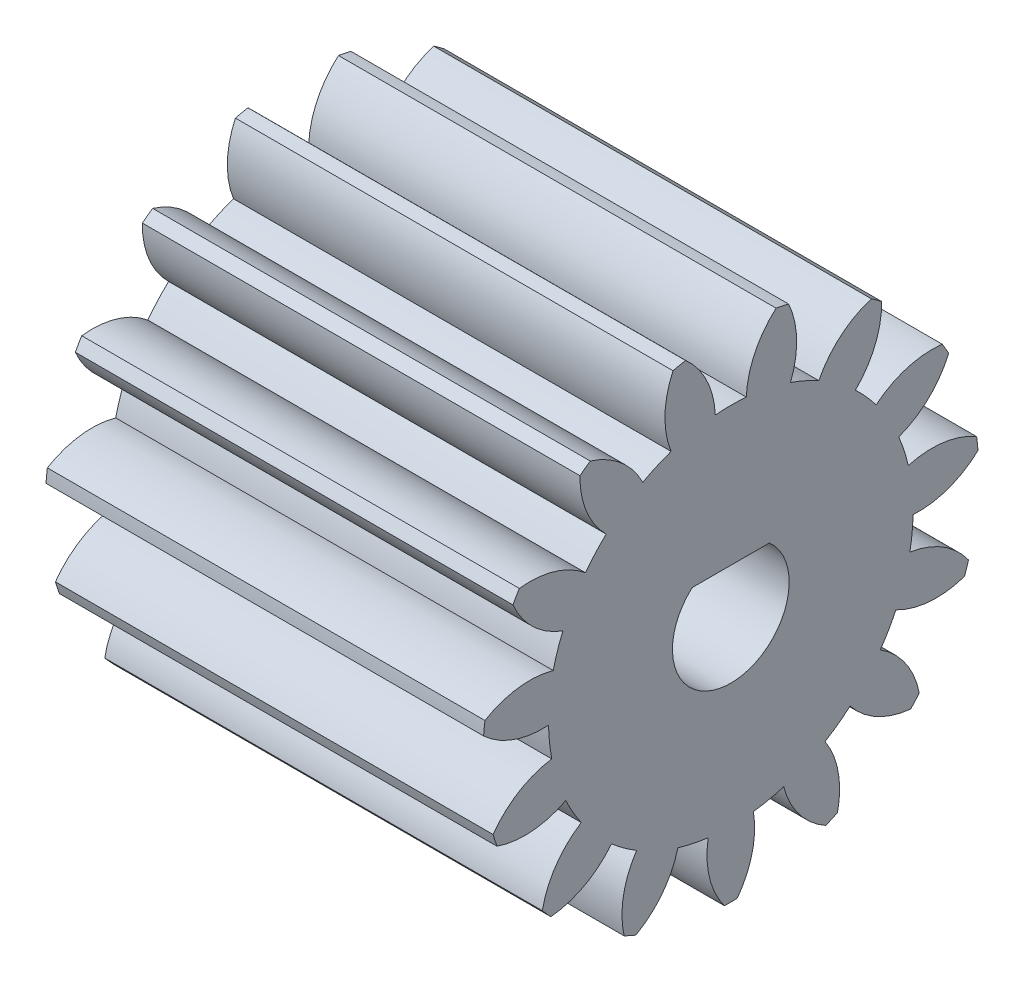
SolidWorks part; units mm, degrees
ref_plane "Plane1" through (0, 0, 0) normal (0, 0, 1) x (1, 0, 0)
ref_plane "Plane2" through (0, 0, 0) normal (0, 1, 0) x (1, 0, 0)
ref_plane "Plane3" through (0, 0, 0) normal (1, 0, 0) x (0, 0, -1)
sketch "HoldingSke" plane through (0, 0, 0) normal (0, 1, 0) x (1, 0, 0)
  line L0 (0, 0) -> (0.9659, -0.2588)
  line L1 (-15, 0) -> (100, 0) construction
  line L2 (0, 0) -> (-2.1039, 2.3779)
  line L3 (0, 0) -> (-11.863, 4.5341)
  line L4 (0, 0) -> (8.3417, 2.2352)
  line L5 (0, 0) -> (-46.8476, -17.4728)
  line L6 (0, 0) -> (-12.4344, -8.3896)
  line L7 (-2.1039, 2.3779) -> (8.6586, 51.2059)
  line L8 (-76.2, 54.61) -> (-75.5, 54.61)
  line L9 (-71.009, 38.7566) -> (-53.1078, 45.2721)
  line L10 (-76.2, 71.12) -> (104.1128, 71.12)
  line L11 (0, 0) -> (-15, 0)
  line L12 (-76.2, 101.6) -> (-76.162, 101.6)
  line L13 (24.9733, 27.94) -> (52.9518, 28.4284)
  line L14 (24.9733, 27.94) -> (24.9743, 27.94)
  line L15 (24.9733, 27.94) -> (100.4006, 29.5858)
  line L16 (-63.627, -1) -> (-12.827, -1)
  circle A0 centre (0, 0) radius 2
  circle A1 centre (0, 0) radius 6.249
  circle A2 centre (0, 0) radius 37.5
  circle A3 centre (0, 0) radius 2
  dimension "Num_teeth" = 15
  dimension "Pitch_radius" = 180.3128
  dimension "Width" = 15
  dimension "Thickness" = 15
sketch "BasProSke" plane through (0, 0, 0) normal (0, 1, 0) x (1, 0, 0)
  line L0 (-10, 0) -> (60, 0) construction
  line L1 (0, 0) -> (0, 8.5)
  line L2 (0, 0) -> (15, 0)
  line L3 (15, 0) -> (15, 8.5)
  line L4 (15, 8.5) -> (0, 8.5)
  dimension "Thickness" = 15
  dimension "Diameter" = 17
revolve "Base-Revolve" add sketch "BasProSke" angle 360 about L0
sketch "TooCutSke" plane through (0, 0, 0) normal (1, 0, 0) x (0, 0, -1)
  line L1 (0, 0) -> (0, 107) construction
  line L2 (0, 0) -> (-0.8504, 7.4516) construction
  line L3 (0, 0) -> (-3.1044, 14.6049) construction
  line L4 (-0.8504, 7.4516) -> (-1.5522, 7.3025) construction
  arc A0 (0.5316, 6.2263) -> (-0.5316, 6.2263) centre (0, 0) ccw
  arc A1 (1.5766, 8.3784) -> (-1.5766, 8.3784) centre (0, 0) ccw
  circle A2 centre (0, 0) radius 7.5 construction
  circle A3 centre (0, 0) radius 7.0477 construction
  arc A4 (-0.5316, 6.2263) -> (-1.5766, 8.3784) centre (-3.5289, 6.1005) ccw
  arc A5 (1.5766, 8.3784) -> (0.5316, 6.2263) centre (3.5289, 6.1005) ccw
extrude "ToothCut" cut sketch "TooCutSke" along normal through all
fillet "Breaks" [suppressed] radius 0.02 tangent propagation no
fillet "RootFillets" [suppressed] radius 0.251
pattern_circular "TeethCuts" count 15 every 24 about axis through (-10, 0, 0) along (1, 0, 0) of "ToothCut", "RootFillets", "Breaks"
sketch "HubNeaOneSke" plane through (0, 0, 0) normal (-1, 0, 0) x (0, 0, 1)
  circle A0 centre (0, 0) radius 6.249
  dimension "Diameter" = 12.498
extrude "HubNearOne" [suppressed] add sketch "HubNeaOneSke" along normal blind 35.0001
sketch "HubNeaBotSke" plane through (0, 0, 0) normal (-1, 0, 0) x (0, 0, 1)
  circle A0 centre (0, 0) radius 6.249
  dimension "Diameter" = 12.498
extrude "HubNearBoth" [suppressed] add sketch "HubNeaBotSke" along normal blind 17.5
ref_plane "FarPln" through (15, 0, 0) normal (1, 0, 0) x (0, 0, -1)
sketch "HubFarSke" plane through (15, 0, 0) normal (1, 0, 0) x (0, 0, -1)
  circle A0 centre (0, 0) radius 6.249
  dimension "Diameter" = 12.498
extrude "HubFar" [suppressed] add sketch "HubFarSke" along normal blind 17.5
sketch "BorSke" plane through (0, 0, 0) normal (1, 0, 0) x (0, 0, -1)
  circle A0 centre (0, 0) radius 2
  dimension "Diameter" = 4
extrude "Bore" cut sketch "BorSke" along normal mid plane 100.0001
sketch "KeySke" plane through (0, 0, 0) normal (1, 0, 0) x (0, 0, -1)
  line L0 (-0.8, 0) -> (-0.8, 2.7)
  line L1 (-0.8, 2.7) -> (0.8, 2.7)
  line L2 (0.8, 2.7) -> (0.8, 0)
  line L3 (0, 0) -> (0, 34) construction
  line L4 (-0.8, 0) -> (0.8, 0)
  dimension "Width" = 1.6
extrude "Keyway" [suppressed] cut sketch "KeySke" along normal mid plane 100.0001
pattern_circular "Keyway2" [suppressed] count 2 every 90 about axis through (-10, 0, 0) along (1, 0, 0) reverse direction yes
sketch "Sketch1" plane through (15, 0, 0) normal (1, 0, 0) x (0, 0, -1)
  line L0 (0, -2) -> (0, 1.5) construction
  line L1 (-1.3229, 1.5) -> (1.3229, 1.5)
  circle A0 centre (0, 0) radius 2 construction
  arc A1 (-1.3229, 1.5) -> (1.3229, 1.5) centre (0, 0) cw
extrude "Boss-Extrude1" add sketch "Sketch1" against normal blind 15 contours A1 L1 region at (15, 1.7023, 0)
equation "' \"Module@HoldingSke\" = 6.35"
equation "' \"Num_teeth@HoldingSke\" = 12"
equation "' \"Ap@HoldingSke\" =  20"
equation "' \"Ap@HoldingSke\" = 20"
equation "' \"Width@HoldingSke\" = 0.5 * 25.4"
equation "' \"Hub_dia@HoldingSke\"= 1 * 25.4"
equation "' \"Hub_dia@HoldingSke\" = 1 * 25.4"
equation "' \"Overall_len@HoldingSke\" = 1.0 * 25.4"
equation "' \"Bore@HoldingSke\" = 0.75 * 25.4"
equation "' \"T_dim@HoldingSke\" = 0.1 * 25.4"
equation "' \"Width@KeySke\" = 0.25 * 25.4"
equation "' \"Show_teeth@HoldingSke\" = 13"
equation "' \"Backlash@HoldingSke\" = 0.009 * 25.4"
equation "' \"Addendum_fac@HoldingSke\" = 1.0"
equation "' \"Dedendum_fac@HoldingSke\" = 1.25"
equation "' \"Dedendum_add@HoldingSke\" = 0.00005 * 25.4"
equation "' \"Clearance_fac@HoldingSke\" = 0.25"
equation "\"Pitch@HoldingSke\" = 1 / \"Module@HoldingSke\""
equation "\"Overcut_dia@TooCutSke\" = (\"Num_teeth@HoldingSke\" + 2 * \"Addendum_fac@HoldingSke\") / \"Pitch@HoldingSke\" + 0.002 * 25.4"
equation "\"Pitch_dia@TooCutSke\" = \"Num_teeth@HoldingSke\" / \"Pitch@HoldingSke\""
equation "\"Base_dia@TooCutSke\" = \"Num_teeth@HoldingSke\" / \"Pitch@HoldingSke\" * cos((\"Ap@HoldingSke\"  * 3.14159265 / 180))"
equation "\"Root_dia@TooCutSke\" = (\"Num_teeth@HoldingSke\" + 2) / \"Pitch@HoldingSke\" - 2 * (\"Addendum_fac@HoldingSke\" + \"Dedendum_fac@HoldingSke\") / \"Pitch@HoldingSke\" - \"Dedendum_add@HoldingSke\" * 2"
equation "\"Half_ang@TooCutSke\" = 180 / \"Num_teeth@HoldingSke\""
equation "\"Half_CT@TooCutSke\" = \"Num_teeth@HoldingSke\" / \"Pitch@HoldingSke\" * sin((3.14159265 / 2 / \"Num_teeth@HoldingSke\")) / 2 - 7 * \"Backlash@HoldingSke\" / 4"
equation "\"Flank_rad@TooCutSke\" = \"Num_teeth@HoldingSke\" / \"Pitch@HoldingSke\" / 5"
equation "\"Radius@RootFillets\" = \"Clearance_fac@HoldingSke\" / \"Pitch@HoldingSke\" + \"Dedendum_add@HoldingSke\""
equation "\"Break_rad@Breaks\" = 0.02 / \"Pitch@HoldingSke\""
equation "\"Thickness@HoldingSke\" = \"Width@HoldingSke\""
equation "\"OAL@HoldingSke\" = \"Thickness@HoldingSke\""
equation "\"MHD@HoldingSke\" = (\"Num_teeth@HoldingSke\" + 2) / \"Pitch@HoldingSke\" - 2 * (\"Addendum_fac@HoldingSke\" + \"Dedendum_fac@HoldingSke\")  / \"Pitch@HoldingSke\" - \"Dedendum_add@HoldingSke\" * 2"
equation "\"MBD@HoldingSke\" = (\"Num_teeth@HoldingSke\" + 2) / \"Pitch@HoldingSke\" - 2 * (\"Addendum_fac@HoldingSke\" + \"Dedendum_fac@HoldingSke\")  / \"Pitch@HoldingSke\" - \"Dedendum_add@HoldingSke\" * 2 - 0.002 * 25.4"
equation "\"MHD@HoldingSke\" = ((sgn( \"MHD@HoldingSke\" - \"Hub_dia@HoldingSke\" )-1)*( \"MHD@HoldingSke\" - \"Hub_dia@HoldingSke\" ))/-2+ \"Hub_dia@HoldingSke\""
equation "\"MBD@HoldingSke\" = ((sgn( \"MBD@HoldingSke\" - \"Bore@HoldingSke\" )-1)*( \"MBD@HoldingSke\" - \"Bore@HoldingSke\" ))/-2+ \"Bore@HoldingSke\""
equation "\"OAL@HoldingSke\" = ((sgn( \"OAL@HoldingSke\" - \"Overall_len@HoldingSke\" )+1)*( \"OAL@HoldingSke\" - \"Overall_len@HoldingSke\" ))/2 + \"Overall_len@HoldingSke\" + 0.000002 * 25.4"
equation "\"Num_teeth@TeethCuts\" = int( \"Show_teeth@HoldingSke\" ) + 1"
equation "\"Num_teeth@TeethCuts\" = ((sgn( \"Num_teeth@TeethCuts\" - \"Num_teeth@HoldingSke\" )-1)*( \"Num_teeth@TeethCuts\" - \"Num_teeth@HoldingSke\" ))/-2+ \"Num_teeth@HoldingSke\""
equation "\"Num_teeth@TeethCuts\" = ((sgn( \"Num_teeth@TeethCuts\" - 2.0)+1)*( \"Num_teeth@TeethCuts\" - 2.0))/2 +2.0"
equation "\"Angle@TeethCuts\" = 360.0 / \"Num_teeth@HoldingSke\""
equation "\"Diameter@BasProSke\" = (\"Num_teeth@HoldingSke\" + 2 * \"Addendum_fac@HoldingSke\") / \"Pitch@HoldingSke\""
equation "\"Thickness@BasProSke\"  = \"Thickness@HoldingSke\""
equation "' \"Fillet_rad@BasProSke\" =  \"Thickness@HoldingSke\" * 0.05"
equation "' \"Fillet_rad@BasProSke\" = \"Thickness@HoldingSke\" * 0.05"
equation "\"MHD@HoldingSke\" = ((sgn( \"MHD@HoldingSke\" - \"Root_dia@TooCutSke\" )-1)*( \"MHD@HoldingSke\" - \"Root_dia@TooCutSke\" ))/-2+ \"Root_dia@TooCutSke\""
equation "\"Diameter@HubNeaOneSke\" = \"MHD@HoldingSke\""
equation "\"Length@HubNearOne\" = \"OAL@HoldingSke\" - \"Thickness@BasProSke\""
equation "\"Diameter@HubNeaBotSke\" = \"MHD@HoldingSke\""
equation "\"Length@HubNearBoth\" = ( \"OAL@HoldingSke\" - \"Thickness@BasProSke\" ) / 2.0"
equation "\"Thickness@FarPln\" = \"Thickness@BasProSke\""
equation "\"Diameter@HubFarSke\" = \"MHD@HoldingSke\""
equation "\"Length@HubFar\" = ( \"OAL@HoldingSke\" - \"Thickness@BasProSke\" ) / 2.0"
equation "\"Diameter@BorSke\" = \"MBD@HoldingSke\""
equation "\"D1@Bore\" = \"OAL@HoldingSke\" * 2.0"
equation "\"D1@Keyway\" = \"OAL@HoldingSke\" * 2.0"
equation "\"Offset@KeySke\" = \"T_dim@HoldingSke\" + \"MBD@HoldingSke\" / 2.0"
